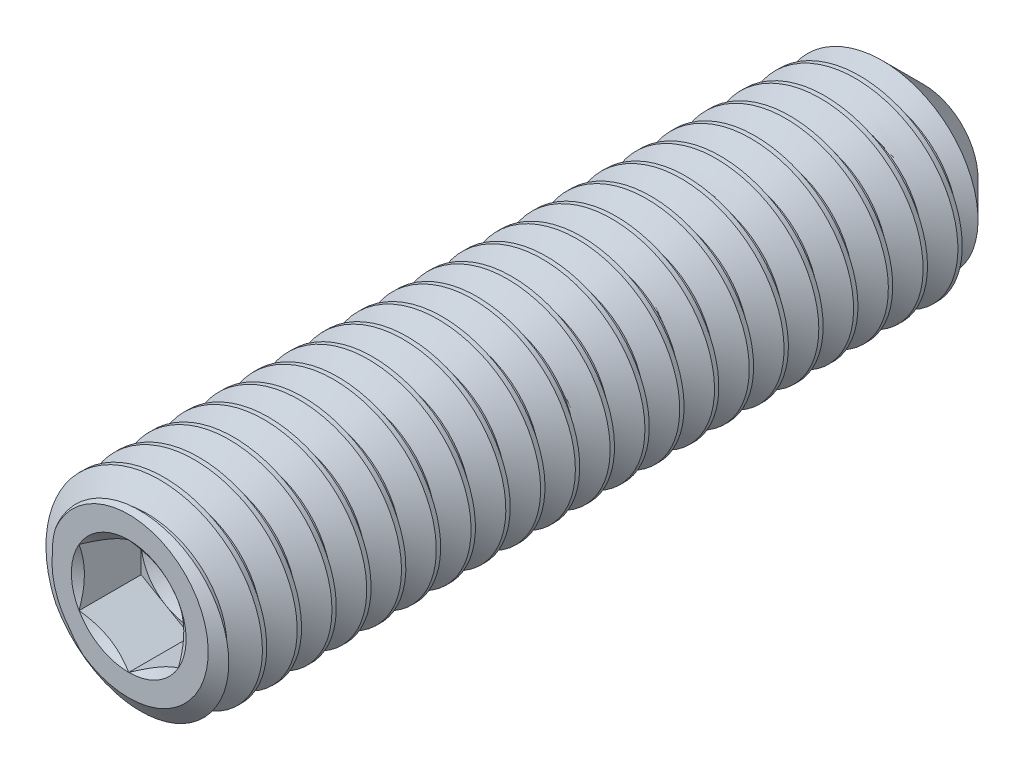
SolidWorks part; units mm, degrees
ref_plane "Front" through (0, 0, 0) normal (0, 0, 1) x (1, 0, 0)
ref_plane "Top" through (0, 0, 0) normal (0, 1, 0) x (1, 0, 0)
ref_plane "Right" through (0, 0, 0) normal (1, 0, 0) x (0, 0, -1)
sketch "Body Sketch" plane through (0, 0, 0) normal (1, 0, 0) x (0, 0, -1)
  line L0 (-7.6707, 0) -> (-7.6707, 1.6)
  line L1 (-7.6707, 1.6) -> (-7.3907, 2)
  line L2 (-7.3907, 2) -> (7.4252, 2)
  line L3 (7.4252, 2) -> (8.3293, 1.0959)
  line L4 (0.0173, 2) -> (0.0173, -2) construction
  line L5 (7.6707, 0) -> (-7.6707, 0)
  line L6 (-7.6707, 1.6) -> (-7.6707, -1.6) construction
  line L7 (7.6707, 0) -> (8.3293, 1.0959)
  line L8 (7.6707, 0) -> (8.3293, -1.0959) construction
  line L10 (7.6707, 0) -> (8.3293, 0) construction
  line L11 (8.3293, 1.0959) -> (8.3293, 0) construction
  point P11 (0.0173, 0)
  dimension "Length" = 16
  dimension "Top Chamfer" = 35
  dimension "Diameter" = 4
  dimension "D1" = 3.2
  dimension "D2" = 118
  dimension "D3" = 45
revolve "Body Revolve" add sketch "Body Sketch" angle 360 about L5
ref_plane "Bottom of Tip Plane" through (0, 0, -8.3293) normal (0, 0, 1) x (1, 0, 0)
sketch "Spiral Sketch" plane through (0, 0, -8.3293) normal (0, 0, 1) x (1, 0, 0)
  circle A0 centre (0, 0) radius 2 construction
  circle A1 centre (0, 0) radius 2
curve "Helix/Spiral" pitch 0.7 height 16.7 radius 2 centre (0, 0, -8.3293) axis (0, 0, 1) start towards (0, 1, 0) parameters "Thread Pitch"=0.7
sketch "Cut Sweep Sketch" plane through (0, 0, 0) normal (1, 0, 0) x (0, 0, -1)
  line L0 (8.3293, 2) -> (8.9418, 2)
  line L1 (8.9418, 2) -> (8.6793, 1.5453)
  line L2 (8.6793, 1.5453) -> (8.5918, 1.5453)
  line L3 (8.5918, 1.5453) -> (8.3293, 2)
  line L4 (8.4605, 1.7727) -> (8.8105, 1.7727) construction
  line L6 (-7.3907, 2) -> (7.4252, 2) construction
  dimension "D1" = 0.0875
  dimension "D3" = 60
  dimension "D2" = 0.35
sweep "Cut Sweep" cut profiles "Cut Sweep Sketch" path "Helix/Spiral" align with end faces yes
sketch "Hex Sketch" plane through (0, 0, 7.6707) normal (0, 0, 1) x (1, 0, 0)
  line L1 (0, 1.1547) -> (-1, 0.5774)
  line L2 (-1, 0.5774) -> (-1, -0.5774)
  line L3 (-1, -0.5774) -> (0, -1.1547)
  line L4 (0, -1.1547) -> (1, -0.5774)
  line L5 (1, -0.5774) -> (1, 0.5774)
  line L6 (1, 0.5774) -> (0, 1.1547)
  circle A0 centre (0, 0) radius 1 construction
  dimension "Hex" = 2
extrude "Hex Extrude" cut sketch "Hex Sketch" against normal blind 1.25
sketch "Hex Entry Sketch" plane through (0, 0, 7.6707) normal (0, 0, 1) x (1, 0, 0)
  circle A0 centre (0, 0) radius 1.1547
extrude "Hex Entry Extrude" cut sketch "Hex Entry Sketch" against normal through all draft 55
sketch "Hex Bottom Sketch" plane through (0, 0, 6.4207) normal (0, 0, 1) x (1, 0, 0)
  circle A0 centre (0, 0) radius 1 construction
  circle A1 centre (0, 0) radius 1
extrude "Hex Bottom Extrude" cut sketch "Hex Bottom Sketch" against normal through all draft 60
equation "\"D1@Cut Sweep Sketch\" = \"Thread Pitch@Helix/Spiral\" * .125"
equation "\"D2@Cut Sweep Sketch\" = \"Thread Pitch@Helix/Spiral\" * .5"
equation "\"D3@Helix/Spiral\" = \"Length@Body Sketch\" + \"Thread Pitch@Helix/Spiral\""
equation "\"hex Depth@Hex Extrude\" = \"Hex@Hex Sketch\" * .625"
equation "\"D1@Body Sketch\" = \"Diameter@Body Sketch\" * .8"
equation "\"Diameter\"= 4mm"
equation "\"Thread Pitch\"= 0.7mm"
equation "\"Hex Size\"= 2.0mm"
equation "\"Diameter@Body Sketch\"=\"Diameter\""
equation "\"Thread Pitch@Helix/Spiral\"=\"Thread Pitch\""
equation "\"Hex@Hex Sketch\"=\"Hex Size\""
